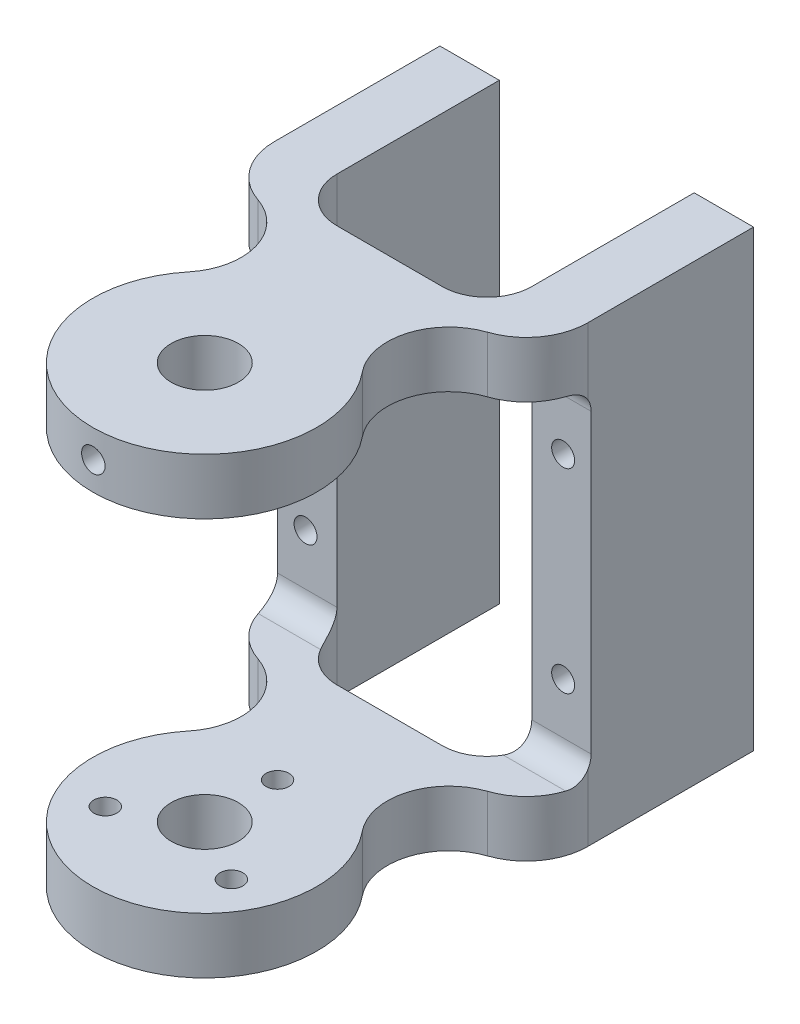
SolidWorks part; units mm, degrees
material "7075-T6 (SN)"
ref_plane "Face" through (0, 0, 0) normal (0, 0, 1) x (1, 0, 0)
ref_plane "Dessus" through (0, 0, 0) normal (0, 1, 0) x (1, 0, 0)
ref_plane "Droite" through (0, 0, 0) normal (1, 0, 0) x (0, 0, -1)
sketch "Esquisse3" plane through (0, 0, 0) normal (0, 1, 0) x (1, 0, 0)
  line L0 (-14, 0) -> (-14, -35)
  line L1 (0, 0) -> (0, -35) construction
  line L3 (14, -35) -> (14, 0)
  line L4 (-14, 0) -> (14, 0)
  line L6 (-14, 0) -> (-14, 3.841) construction
  line L7 (14, 0) -> (14, 6.0564) construction
  circle A0 centre (0, -35) radius 3
  arc A1 (-14, -35) -> (14, -35) centre (0, -35) ccw
  dimension "D2" = 6
  dimension "D1" = 28
  dimension "D4" = 35
extrude "Boss.-Extru.1" add sketch "Esquisse3" along normal mid plane 40.5
sketch "Esquisse5" plane through (0, 0, 0) normal (1, 0, 0) x (0, 0, -1)
  line L1 (-49, 15.25) -> (-24.5, 15.25)
  line L6 (-24.5, 15.25) -> (-24.5, -15.25)
  line L7 (-24.5, -15.25) -> (-49, -15.25)
  line L8 (-49, 20.25) -> (-49, -20.25) construction
  line L9 (-49, -15.25) -> (-49, 15.25)
  line L10 (-35, 20.25) -> (-49, 20.25) construction
  line L11 (-49, -20.25) -> (-35, -20.25) construction
  dimension "D1" = 5
  dimension "D2" = 5
  dimension "D3" = 24.5
extrude "Enlèv. mat.-Extru.2" cut sketch "Esquisse5" against normal through all and the other way through all
sketch "Esquisse6" plane through (0, -20.25, 0) normal (0, 1, 0) x (1, 0, 0)
  line L0 (-9, 0) -> (-9, -18) construction
  line L1 (-9, -18) -> (9, -18) construction
  line L2 (-8.7, 0) -> (-8.7, -14.5)
  line L5 (-4.7, -18.5) -> (4.7, -18.5)
  line L7 (14, -35) -> (14, 0) construction
  line L8 (9, -18) -> (9, 0) construction
  line L9 (9, 0) -> (-9, 0) construction
  line L11 (0, 0) -> (0, -37) construction
  line L12 (0, -35) -> (14, -26.9171) construction
  line L13 (-14, 0) -> (-14, -35) construction
  line L14 (8.7, -14.5) -> (8.7, 0)
  line L15 (14, 0) -> (-14, 0) construction
  line L16 (8.7, 0) -> (-8.7, 0)
  arc A0 (-8.7, -14.5) -> (-4.7, -18.5) centre (-4.7, -14.5) ccw
  arc A1 (4.7, -18.5) -> (8.7, -14.5) centre (4.7, -14.5) ccw
  point P4 (0, -18.5)
  point P6 (8.7, -18.5)
  point P10 (-8.7, -18.3277)
  point P13 (0, 0)
  point P14 (0, 0)
  point P15 (8.5867, -18.5)
  dimension "D1" = 18
  dimension "D2" = 4
  dimension "D6" = 5.3
  dimension "D8" = 18.5
extrude "Enlèv. mat.-Extru.3" cut sketch "Esquisse6" against normal through all and the other way through all
sketch "Esquisse11" plane through (0, -20.25, 0) normal (0, -1, 0) x (1, 0, 0)
  line L0 (0, 49) -> (0, 14.7927) construction
  line L1 (-14, 0) -> (-14, 35) construction
  line L3 (14, 14.7927) -> (14, 35)
  line L4 (14, 35) -> (14, 0) construction
  line L5 (-14, 14.7927) -> (14, 14.7927) construction
  line L6 (-14, 14.7927) -> (-14, 35)
  arc A0 (7.7551, 28.6866) -> (-7.7551, 28.6866) centre (0, 35) ccw
  arc A1 (-10.2602, 20.0035) -> (-14, 14.7927) centre (-8.5, 14.7927) ccw
  arc A2 (7.7551, 28.6866) -> (10.2602, 20.0035) centre (12.0203, 25.2142) ccw
  arc A3 (14, 35) -> (-14, 35) centre (0, 35) ccw construction
  arc A4 (14, 35) -> (-14, 35) centre (0, 35) ccw
  arc A5 (-7.7551, 28.6866) -> (-10.2602, 20.0035) centre (-12.0203, 25.2142) cw
  arc A6 (10.2602, 20.0035) -> (14, 14.7927) centre (8.5, 14.7927) cw
  dimension "D1" = 20
  dimension "D2" = 5.5
extrude "Enlèv. mat.-Extru.6" cut sketch "Esquisse11" against normal through all
hole_wizard "Trou taraudé M2.51" positions "Esquisse13" profile "Esquisse12" tap size "M2.5" standard "DIN" end condition up to next
sketch "Esquisse13" plane through (0, -20.25, 0) normal (0, 1, 0) x (1, 0, 0)
  line L0 (0, -28.5) -> (-5.6292, -38.25)
  line L1 (-5.6292, -38.25) -> (5.6292, -38.25)
  line L2 (5.6292, -38.25) -> (0, -28.5)
  line L4 (-3, -35) -> (-6.5, -35) construction
  circle A0 centre (0, -35) radius 6.5
  circle A1 centre (0, -35) radius 3 construction
  point P6 (0, -28.5)
  point P7 (-5.6292, -38.25)
  point P9 (5.6292, -38.25)
  dimension "D1" = 13
sketch "Esquisse12" plane through (0, -20.25, 28.5) normal (1, 0, 0) x (0, 0, -1)
  line L0 (0, 0) -> (0, 5)
  line L1 (0, 5) -> (1.025, 5)
  line L2 (1.025, 5) -> (1.025, 0)
  line L5 (1.025, 0) -> (0, 0)
  line L11 (0, -6.35) -> (0, 107.95) construction
  dimension "Diamètre du trou pour taraudage jusqu'au prochain" = 2.05
  dimension "Profondeur du trou pour taraudage jusqu'au prochain" = 5
cosmetic thread "Filetage de perçage1" parameters "D1"=5, "D2"=2.5
cosmetic thread "Filetage de perçage2" parameters "D1"=5, "D2"=2.5
cosmetic thread "Filetage de perçage3" parameters "D1"=5, "D2"=2.5
ref_plane "Plan1" through (0, 0, 45) normal (0, 0, 1) x (1, 0, 0)
hole_wizard "Diamètre du perçage Ø2.1 (2.1)1" positions "Esquisse15" profile "Esquisse14" hole size "Ø2.1" standard "DIN"
sketch "Esquisse15" plane through (0, 0, 45) normal (0, 0, 1) x (1, 0, 0)
  line L0 (0, 20.25) -> (0, 15.25) construction
  line L4 (10, 20.25) -> (-10, 20.25) construction
  line L5 (-10, 15.25) -> (10, 15.25) construction
  point P0 (0, 17.75)
sketch "Esquisse14" plane through (0, 17.75, 45) normal (1, 0, 0) x (0, -1, 0)
  line L0 (0, 0) -> (0, 2.4309)
  line L1 (0, 2.4309) -> (1.05, 1.8)
  line L2 (1.05, 1.8) -> (1.05, 0)
  line L5 (1.05, 0) -> (0, 0)
  line L10 (0, 2.4309) -> (-1.05, 1.8) construction
  line L11 (0, -6.35) -> (0, 107.95) construction
  dimension "Diamètre du perçage" = 2.1
  dimension "Profondeur du perçage" = 1.8
  dimension "Angle de pointe" = 118
sketch "Esquisse16" plane through (0, 0, 0) normal (0, 0, -1) x (-1, 0, 0)
  line L0 (0, 23.0718) -> (0, -4.4703) construction
  line L4 (-17.4288, 0) -> (26.647, 0) construction
  circle A0 centre (-11.5, 8.7) radius 1.025
  circle A1 centre (11.5, 8.7) radius 1.025
  circle A2 centre (-11.5, -8.7) radius 1.025
  circle A3 centre (11.5, -8.7) radius 1.025
  dimension "D2" = 8.7
  dimension "D3" = 2.05
  dimension "D4" = 2.05
  dimension "D5" = 2.05
  dimension "D6" = 2.05
  dimension "D7" = 17.4
  dimension "D8" = 8.7
  dimension "D1" = 17.4
  dimension "D9" = 23
  dimension "D10" = 23
  dimension "D11" = 11.5
extrude "Enlèv. mat.-Extru.7" cut sketch "Esquisse16" against normal through all
sketch "Esquisse19" plane through (0, 0, 24.5) normal (0, 0, 1) x (1, 0, 0)
  line L0 (-6.5669, -15.25) -> (6.5669, -15.25) construction
  line L1 (-15, 15.25) -> (15, 15.25)
  line L2 (-15, 15.25) -> (-15, -15.25)
  line L3 (-15, -15.25) -> (15, -15.25)
  line L4 (15, 15.25) -> (15, -15.25)
  line L5 (-6.5669, 15.25) -> (6.5669, 15.25) construction
  line L6 (0, 10.4807) -> (0, -9.59) construction
  dimension "D1" = 30
  dimension "D2" = 15
extrude "Enlèv. mat.-Extru.11" cut sketch "Esquisse19" against normal blind 10
fillet "Congé1" radius 2 4 edges at (11.35, -15.25, 14.5) (-11.35, -15.25, 14.5) (11.35, 15.25, 14.5) (-11.35, 15.25, 14.5)
